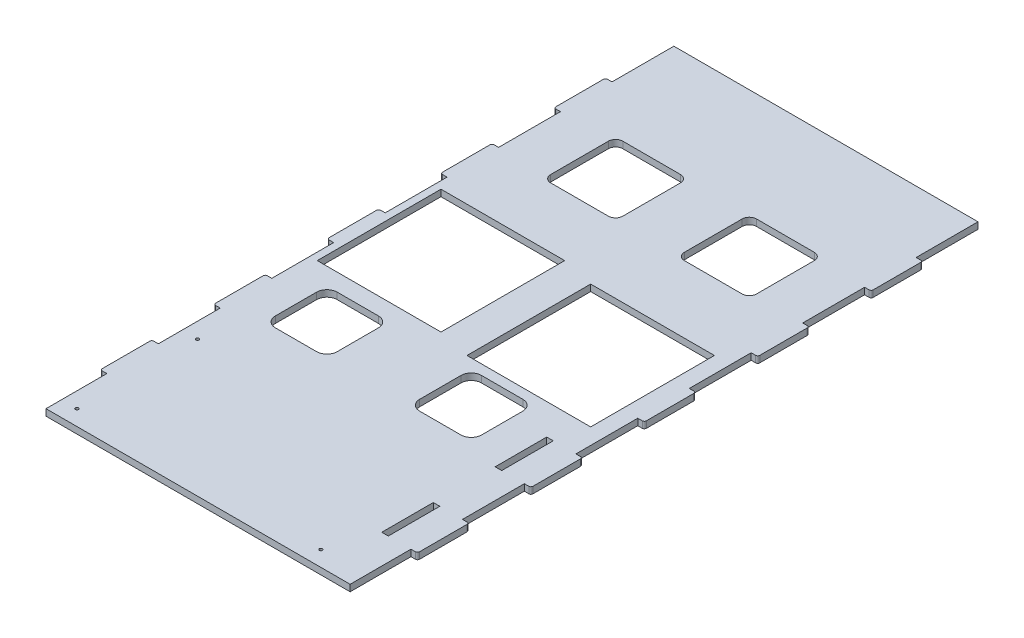
SolidWorks part; units mm, degrees
material "Beech"
ref_plane "Front Plane" through (0, 0, 0) normal (0, 0, 1) x (1, 0, 0)
ref_plane "Top Plane" through (0, 0, 0) normal (0, 1, 0) x (1, 0, 0)
ref_plane "Right Plane" through (0, 0, 0) normal (1, 0, 0) x (0, 0, -1)
sketch "Sketch1" plane through (0, 0, 0) normal (0, 1, 0) x (1, 0, 0)
  line L1 (0, 0) -> (295, 0)
  line L2 (0, 0) -> (0, 59)
  line L3 (0, 609) -> (295, 609)
  line L4 (295, 0) -> (295, 59)
  line L5 (0, 59) -> (-6.35, 59)
  line L7 (0, 109) -> (-6.35, 109)
  line L8 (-6.35, 59) -> (-6.35, 109)
  line L9 (0, 169) -> (-6.35, 169)
  line L10 (-6.35, 169) -> (-6.35, 219)
  line L11 (0, 219) -> (-6.35, 219)
  line L13 (0, 279) -> (-6.35, 279)
  line L14 (-6.35, 279) -> (-6.35, 329)
  line L15 (0, 329) -> (-6.35, 329)
  line L17 (0, 389) -> (-6.35, 389)
  line L18 (-6.35, 389) -> (-6.35, 439)
  line L19 (0, 439) -> (-6.35, 439)
  line L21 (0, 499) -> (-6.35, 499)
  line L22 (-6.35, 499) -> (-6.35, 549)
  line L23 (0, 549) -> (-6.35, 549)
  line L25 (295, 59) -> (301.35, 59)
  line L27 (295, 109) -> (301.35, 109)
  line L28 (301.35, 59) -> (301.35, 109)
  line L29 (295, 169) -> (301.35, 169)
  line L30 (301.35, 169) -> (301.35, 219)
  line L31 (295, 219) -> (301.35, 219)
  line L33 (295, 279) -> (301.35, 279)
  line L34 (301.35, 279) -> (301.35, 329)
  line L35 (295, 329) -> (301.35, 329)
  line L37 (295, 389) -> (301.35, 389)
  line L38 (301.35, 389) -> (301.35, 439)
  line L39 (295, 439) -> (301.35, 439)
  line L41 (295, 499) -> (301.35, 499)
  line L42 (301.35, 499) -> (301.35, 549)
  line L43 (295, 549) -> (301.35, 549)
  line L44 (0, 549) -> (0, 609)
  line L46 (0, 329) -> (0, 389)
  line L49 (0, 219) -> (0, 279)
  line L50 (0, 109) -> (0, 169)
  line L51 (295, 109) -> (295, 169)
  line L52 (295, 219) -> (295, 279)
  line L53 (295, 329) -> (295, 389)
  line L54 (295, 439) -> (295, 499)
  line L55 (295, 549) -> (295, 609)
  line L56 (0, 439) -> (0, 499)
  dimension "D1" = 609
  dimension "D2" = 295
  dimension "D3" = 6.35
  dimension "D4" = 50
  dimension "D5" = 59
  dimension "D7" = 60
  dimension "D8" = 50
  dimension "D9" = 6.35
  dimension "D11" = 59
  dimension "D12" = 60
  dimension "D6" = 5
  dimension "D10" = 5
extrude "Boss-Extrude1" add sketch "Sketch1" along normal blind 6.35
fillet "Fillet1" radius 2 20 edges at (301.35, 3.175, -549) (301.35, 3.175, -499) (301.35, 3.175, -439) (301.35, 3.175, -389) (301.35, 3.175, -329) (301.35, 3.175, -279) (301.35, 3.175, -219) (301.35, 3.175, -169) (301.35, 3.175, -109) (301.35, 3.175, -59) (-6.35, 3.175, -59) (-6.35, 3.175, -109) (-6.35, 3.175, -169) (-6.35, 3.175, -219) (-6.35, 3.175, -279) (-6.35, 3.175, -329) (-6.35, 3.175, -389) (-6.35, 3.175, -439) (-6.35, 3.175, -499) (-6.35, 3.175, -549)
sketch "Sketch2" plane through (0, 6.35, 0) normal (0, 1, 0) x (1, 0, 0)
  line L0 (266.65, 0) -> (266.65, 100) construction
  line L1 (0, 0) -> (295, 0) construction
  line L2 (0, 609) -> (0, 0) construction
  line L3 (295, 609) -> (295, 0) construction
  line L4 (0, 150) -> (266.65, 100) construction
  line L5 (266.65, 169) -> (266.65, 219)
  line L6 (266.65, 59) -> (273, 59)
  line L7 (266.65, 59) -> (266.65, 109)
  line L8 (266.65, 109) -> (273, 109)
  line L9 (273, 59) -> (273, 109)
  line L10 (266.65, 169) -> (273, 169)
  line L11 (273, 169) -> (273, 219)
  line L12 (266.65, 219) -> (273, 219)
  line L13 (0, 84.2124) -> (266.65, 84) construction
  line L14 (55.0424, 504.4355) -> (111.0424, 504.4355)
  line L15 (48.0424, 497.4355) -> (48.0424, 441.4355)
  line L16 (55.0424, 434.4355) -> (111.0424, 434.4355)
  line L17 (118.0424, 497.4355) -> (118.0424, 441.4355)
  line L18 (185.2335, 503.9695) -> (241.2335, 503.9695)
  line L19 (178.2335, 496.9695) -> (178.2335, 440.9695)
  line L20 (185.2335, 433.9695) -> (241.2335, 433.9695)
  line L21 (248.2335, 496.9695) -> (248.2335, 440.9695)
  line L22 (43.325, 239.1432) -> (83.325, 239.1432)
  line L23 (33.325, 229.1432) -> (33.325, 189.1432)
  line L24 (43.325, 179.1432) -> (83.325, 179.1432)
  line L25 (93.325, 229.1432) -> (93.325, 189.1432)
  line L26 (33.325, 239.1432) -> (93.325, 179.1432) construction
  line L27 (33.325, 179.1432) -> (93.325, 239.1432) construction
  line L32 (133.325, 0) -> (133.325, 609) construction
  line L33 (295, 609) -> (0, 609) construction
  line L34 (7.1727, 375.936) -> (127.1727, 375.936)
  line L35 (7.1727, 375.936) -> (7.1727, 255.936)
  line L36 (7.1727, 255.936) -> (127.1727, 255.936)
  line L37 (127.1727, 375.936) -> (127.1727, 255.936)
  line L38 (159.4648, 368.8349) -> (279.4648, 368.8349)
  line L39 (159.4648, 368.8349) -> (159.4648, 248.8349)
  line L40 (159.4648, 248.8349) -> (279.4648, 248.8349)
  line L41 (279.4648, 368.8349) -> (279.4648, 248.8349)
  line L42 (233.325, 179.1432) -> (173.325, 239.1432) construction
  line L43 (233.325, 239.1432) -> (173.325, 179.1432) construction
  line L44 (173.325, 229.1432) -> (173.325, 189.1432)
  line L45 (223.325, 179.1432) -> (183.325, 179.1432)
  line L46 (233.325, 229.1432) -> (233.325, 189.1432)
  line L47 (223.325, 239.1432) -> (183.325, 239.1432)
  arc A0 (48.0424, 441.4355) -> (55.0424, 434.4355) centre (55.0424, 441.4355) ccw
  arc A1 (111.0424, 434.4355) -> (118.0424, 441.4355) centre (111.0424, 441.4355) ccw
  arc A2 (111.0424, 504.4355) -> (118.0424, 497.4355) centre (111.0424, 497.4355) cw
  arc A3 (55.0424, 504.4355) -> (48.0424, 497.4355) centre (55.0424, 497.4355) ccw
  arc A4 (178.2335, 440.9695) -> (185.2335, 433.9695) centre (185.2335, 440.9695) ccw
  arc A5 (241.2335, 433.9695) -> (248.2335, 440.9695) centre (241.2335, 440.9695) ccw
  arc A6 (241.2335, 503.9695) -> (248.2335, 496.9695) centre (241.2335, 496.9695) cw
  arc A7 (185.2335, 503.9695) -> (178.2335, 496.9695) centre (185.2335, 496.9695) ccw
  arc A8 (33.325, 189.1432) -> (43.325, 179.1432) centre (43.325, 189.1432) ccw
  arc A9 (83.325, 179.1432) -> (93.325, 189.1432) centre (83.325, 189.1432) ccw
  arc A10 (83.325, 239.1432) -> (93.325, 229.1432) centre (83.325, 229.1432) cw
  arc A11 (43.325, 239.1432) -> (33.325, 229.1432) centre (43.325, 229.1432) ccw
  arc A16 (223.325, 239.1432) -> (233.325, 229.1432) centre (223.325, 229.1432) cw
  arc A17 (183.325, 239.1432) -> (173.325, 229.1432) centre (183.325, 229.1432) ccw
  arc A18 (183.325, 179.1432) -> (173.325, 189.1432) centre (183.325, 189.1432) cw
  arc A19 (233.325, 189.1432) -> (223.325, 179.1432) centre (223.325, 189.1432) cw
  circle A20 centre (15, 15) radius 1.5
  circle A21 centre (251.65, 15) radius 1.5
  circle A22 centre (15, 131.9259) radius 1.5
  point P33 (118.0424, 434.4355)
  point P36 (118.0424, 504.4355)
  point P39 (48.0424, 504.4355)
  point P42 (178.2335, 433.9695)
  point P47 (248.2335, 503.9695)
  point P50 (178.2335, 503.9695)
  point P51 (63.325, 209.1432)
  point P74 (133.325, 84.1062)
  point P99 (203.325, 209.1432)
  dimension "D10" = 7
  dimension "D11" = 7
  dimension "D16" = 10
  dimension "D17" = 70
  dimension "D22" = 3
  dimension "D25" = 3
  dimension "D28" = 3
  dimension "D1" = 100
  dimension "D2" = 150
  dimension "D3" = 6.35
  dimension "D4" = 50
  dimension "D6" = 70
  dimension "D7" = 70
  dimension "D8" = 70
  dimension "D9" = 70
  dimension "D12" = 60
  dimension "D13" = 60
  dimension "D14" = 22
  dimension "D15" = 59
  dimension "12" = 120
  dimension "D19" = 120
  dimension "D20" = 120
  dimension "D21" = 120
  dimension "D23" = 15
  dimension "D24" = 15
  dimension "D26" = 15
  dimension "D27" = 15
  dimension "D29" = 15
  dimension "D30" = 15
  dimension "D5" = 2
extrude "Cut-Extrude1" cut sketch "Sketch2" against normal blind 6.35
